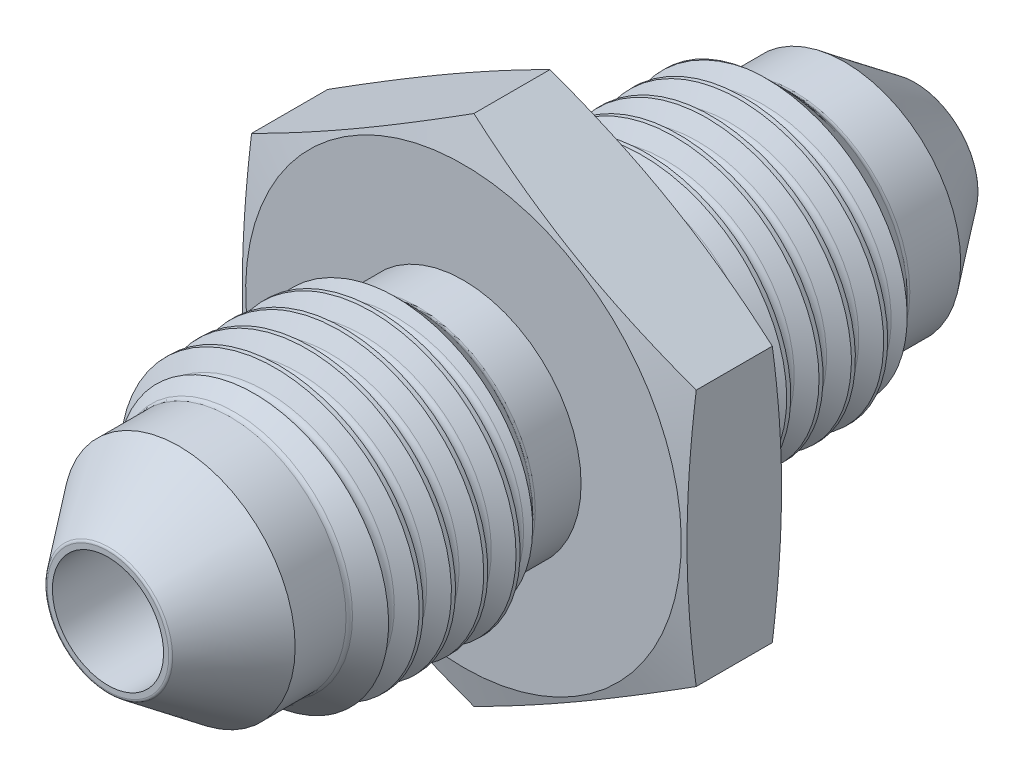
SolidWorks part; units mm, degrees
material "2024-T4"
ref_plane "Front Plane" through (0, 0, 0) normal (0, 0, 1) x (1, 0, 0)
ref_plane "Top Plane" through (0, 0, 0) normal (0, 1, 0) x (1, 0, 0)
ref_plane "Right Plane" through (0, 0, 0) normal (1, 0, 0) x (0, 0, -1)
sketch "Sketch0" plane through (0, 0, 0) normal (1, 0, 0) x (0, 0, -1)
  line L0 (-15.875, 0) -> (0, 0) construction
  line L1 (0, 0) -> (15.875, 0) construction
  line L2 (-10.9728, 5.5562) -> (-10.9728, -5.5562) construction
  line L3 (-15.875, 2.1844) -> (-15.875, -2.1844) construction
  line L4 (-15.875, 2.4511) -> (-15.875, -2.4511) construction
  line L5 (-13.0773, 4.5593) -> (-13.0773, -4.5593) construction
  line L6 (-15.875, 2.4511) -> (-13.0773, 4.5593) construction
  line L7 (-13.0773, 4.5593) -> (-10.9728, 4.5593) construction
  line L8 (-10.9728, 4.5593) -> (-10.9728, -4.5593) construction
  line L9 (-1.905, 8.7376) -> (-1.905, -8.7376) construction
  line L10 (-1.905, 8.5598) -> (-1.905, -8.5598) construction
  line L11 (-10.9728, 4.5593) -> (-10.9728, 5.5562) construction
  line L12 (-10.9728, 5.5562) -> (-3.81, 5.5562) construction
  line L13 (-3.81, 5.5562) -> (-3.81, 4.6228) construction
  line L14 (-3.81, 4.6228) -> (-1.905, 4.6228) construction
  line L15 (-3.81, 4.6228) -> (-3.81, -4.6228) construction
  line L16 (-1.905, 0) -> (-2.032, 0) construction
  point P8 (-1.905, 0)
  point P13 (-13.0773, 0)
  point P14 (-10.9728, 0)
  point P24 (-3.81, 0)
  point P26 (-1.905, 0)
  point P27 (1.905, 0)
  dimension "37" = 37
sketch "Sketch1" plane through (0, 0, 0) normal (1, 0, 0) x (0, 0, -1)
  line L0 (-15.875, 0) -> (0, 0)
  line L1 (-15.875, 0) -> (-15.875, 2.3878)
  line L2 (-15.8244, 2.4892) -> (-13.0773, 4.5593)
  line L3 (-13.0773, 4.5593) -> (-11.078, 4.5593)
  line L4 (-10.8984, 4.6337) -> (-9.9759, 5.5562)
  line L5 (-9.9759, 5.5562) -> (-4.7435, 5.5562)
  line L6 (-4.7435, 5.5562) -> (-3.8844, 4.6972)
  line L7 (-3.7048, 4.6228) -> (0, 4.6228)
  line L8 (0, 4.6228) -> (0, 0)
  line L10 (-10.9728, 5.5562) -> (-10.9728, -5.5562) construction
  line L11 (-19.812, 0) -> (0, 0) construction
  line L12 (-15.875, 2.1844) -> (-15.875, -2.1844) construction
  line L13 (-10.9728, 5.5562) -> (-3.81, 5.5562) construction
  line L15 (-3.81, 5.5562) -> (-3.81, 4.6228) construction
  arc A0 (-15.875, 2.3878) -> (-15.8244, 2.4892) centre (-15.748, 2.3878) cw
  arc A1 (-11.078, 4.5593) -> (-10.8984, 4.6337) centre (-11.078, 4.8133) ccw
  arc A2 (-3.8844, 4.6972) -> (-3.7048, 4.6228) centre (-3.7048, 4.8768) ccw
  point P27 (-15.875, 2.4511)
  point P30 (-10.9728, 4.5593)
  point P33 (-3.81, 4.6228)
  dimension "D1" = 0.127
  dimension "D2" = 0.254
  dimension "D3" = 45
  dimension "D4" = 45
revolve "Revolve1" add sketch "Sketch1" angle 360 about L11
sketch "Sketch2" plane through (0, 0, 15.875) normal (0, 0, 1) x (1, 0, 0)
  circle A0 centre (0, 0) radius 5.5562
  point P3 (0, 5.5562)
curve "Helix/Spiral1" pitch 1.27 height 15.24 radius 5.5562 centre (0, 0, 15.875) axis (0, 0, -1) start towards (0, 1, 0) parameters "Pitch"=1.27
sketch "Sketch3" plane through (0, 0, 0) normal (1, 0, 0) x (0, 0, -1)
  line L0 (-17.0656, 5.6937) -> (-16.4306, 4.5939) construction
  line L1 (-16.4306, 4.5939) -> (-15.7956, 5.6937) construction
  line L2 (-15.7956, 5.6937) -> (-17.0656, 5.6937) construction
  line L3 (-15.875, 5.5562) -> (-16.9862, 5.5562) construction
  line L4 (-16.4306, 5.6937) -> (-16.4306, 5.5562) construction
  line L5 (-16.5629, 4.823) -> (-16.2983, 4.823) construction
  line L6 (-16.4306, 4.823) -> (-16.4306, 4.5939) construction
  line L7 (-17.0259, 5.625) -> (-16.6291, 4.9376)
  line L8 (-17.0259, 5.625) -> (-15.8353, 5.625)
  line L9 (-15.8353, 5.625) -> (-16.2322, 4.9376)
  line L10 (-16.4306, 4.5939) -> (-16.4306, -5.5563) construction
  line L11 (-16.4306, -5.5563) -> (-15.1606, -5.5563) construction
  line L12 (-15.1606, -5.5563) -> (-13.8906, -5.5563) construction
  line L13 (-13.8906, -5.5563) -> (-12.6206, -5.5562) construction
  line L14 (-12.6206, -5.5562) -> (-11.3506, -5.5563) construction
  line L15 (-11.3506, -5.5563) -> (-10.0806, -5.5562) construction
  line L16 (-10.0806, -5.5562) -> (-8.8106, -5.5562) construction
  line L17 (-8.8106, -5.5562) -> (-7.5406, -5.5562) construction
  line L21 (-9.9759, -5.5562) -> (-4.7435, -5.5562) construction
  arc A0 (-16.6291, 4.9376) -> (-16.2322, 4.9376) centre (-16.4306, 5.0522) ccw
  point P13 (-16.4306, 5.625)
sweep "Cut-Sweep1" cut profiles "Sketch3" path "Helix/Spiral1" align with end faces yes
ref_axis "Axis1" through (-10.4775, 0, 0) along (1, 0, 0)
pattern_circular "CirPattern1" count 2 over 180 about axis through (-10.4775, 0, 0) along (1, 0, 0) reverse direction yes of bodies 103
sketch "Sketch4" plane through (0, 0, 0) normal (0, 0, 1) x (1, 0, 0)
  line L1 (0, 10.0893) -> (-8.7376, 5.0447)
  line L2 (-8.7376, 5.0447) -> (-8.7376, -5.0447)
  line L3 (-8.7376, -5.0447) -> (0, -10.0893)
  line L4 (0, -10.0893) -> (8.7376, -5.0447)
  line L5 (8.7376, -5.0447) -> (8.7376, 5.0447)
  line L6 (8.7376, 5.0447) -> (0, 10.0893)
  circle A0 centre (0, 0) radius 8.7376 construction
extrude "Boss-Extrude1" add sketch "Sketch4" along normal up to vertex (1.905 mm away) and the other way up to vertex (1.905 mm away) up to point (0, 0, 1.905) other way up to point (0, 0, -1.905)
sketch "Sketch5" plane through (0, 0, 0) normal (1, 0, 0) x (0, 0, -1)
  line L0 (-1.905, 11.6188) -> (1.905, 11.6188)
  line L1 (-1.905, 11.6188) -> (-1.905, 8.5598)
  line L2 (-1.905, 8.5598) -> (-1.4952, 10.0893)
  line L3 (-1.4952, 10.0893) -> (1.4952, 10.0893)
  line L4 (1.4952, 10.0893) -> (1.905, 8.5598)
  line L5 (1.905, 8.5598) -> (1.905, 11.6188)
  line L7 (-1.905, 10.0893) -> (1.905, 10.0893) construction
  line L8 (-1.905, 0) -> (0, 0) construction
  dimension "D1" = 15
revolve "Cut-Revolve1" cut sketch "Sketch5" angle 360 about L8
sketch "Sketch6" plane through (0, 0, 0) normal (1, 0, 0) x (0, 0, -1)
  line L0 (-15.875, 2.1844) -> (0, 2.1844)
  line L1 (2.1844, 0) -> (-15.875, 0)
  line L2 (-15.875, 0) -> (-15.875, 2.1844)
  arc A0 (0, 2.1844) -> (2.1844, 0) centre (0, 0) cw
revolve "Cut-Revolve2" cut sketch "Sketch6" angle 360 about L1
pattern_circular "CirPattern2" count 2 over 180 about axis through (-10.4775, 0, 0) along (1, 0, 0) of "Cut-Revolve2" reverse direction yes
equation "\"D3@Helix/Spiral1\" = \"Pitch@Helix/Spiral1\" + \"J@Sketch0\""
equation "\"P@Sketch3\" = \"Pitch@Helix/Spiral1\""
equation "\"H/8@Sketch3\" = \"H@Sketch3\" / 8"
equation "\"2/3H@Sketch3\" = 2/3 * \"H@Sketch3\""
